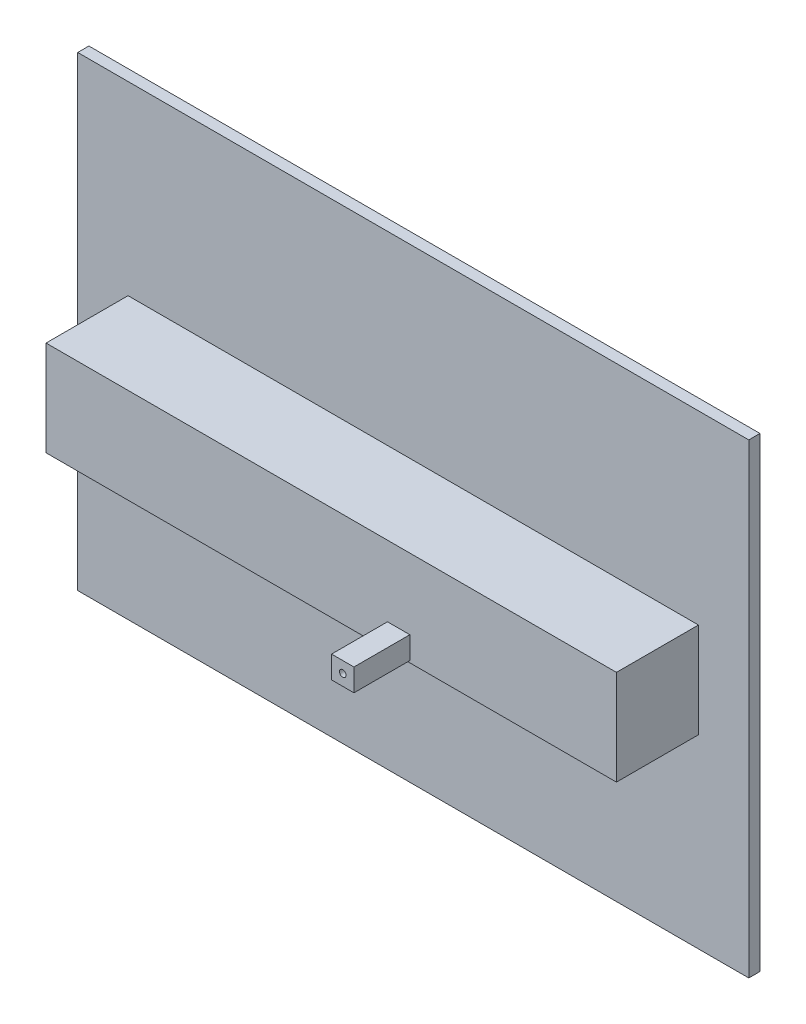
SolidWorks part; units mm, degrees
ref_plane "前视基准面" through (0, 0, 0) normal (0, 0, 1) x (1, 0, 0)
ref_plane "上视基准面" through (0, 0, 0) normal (0, 1, 0) x (1, 0, 0)
ref_plane "右视基准面" through (0, 0, 0) normal (1, 0, 0) x (0, 0, -1)
sketch "草图1" plane through (0, 0, 0) normal (0, 0, 1) x (1, 0, 0)
  line L1 (-90, 62.5) -> (90, 62.5)
  line L2 (-90, 62.5) -> (-90, -62.5)
  line L3 (-90, -62.5) -> (90, -62.5)
  line L4 (90, 62.5) -> (90, -62.5)
  line L5 (-90, 62.5) -> (90, -62.5) construction
  line L6 (-90, -62.5) -> (90, 62.5) construction
  point P0 (0, 0)
  dimension "D1" = 125
  dimension "D2" = 180
extrude "凸台-拉伸1" add sketch "草图1" along normal blind 3
sketch "草图7" plane through (0, 0, 0) normal (0, 0, -1) x (-1, 0, 0)
  line L1 (-74, 10.25) -> (74, 10.25)
  line L2 (-74, 10.25) -> (-74, -10.25)
  line L3 (-74, -10.25) -> (74, -10.25)
  line L4 (74, 10.25) -> (74, -10.25)
  line L5 (0, 0) -> (72.729, 0) construction
  line L8 (0, 0) -> (0, -50.9103) construction
  dimension "D1" = 20.5
  dimension "D2" = 148
extrude "电池位切除-拉伸3" cut sketch "草图7" against normal up to next
sketch "草图8" plane through (0, 0, 3) normal (0, 0, 1) x (1, 0, 0)
  line L12 (74, 10.25) -> (74, -10.25) construction
  line L13 (-76.5, 12.75) -> (76.5, 12.75)
  line L14 (-76.5, 12.75) -> (-76.5, -12.75)
  line L15 (-76.5, -12.75) -> (76.5, -12.75)
  line L16 (76.5, 12.75) -> (76.5, -12.75)
  line L17 (-74, -10.25) -> (-74, 10.25) construction
  line L18 (-74, 10.25) -> (74, 10.25) construction
  line L19 (74, -10.25) -> (-74, -10.25) construction
  line L20 (-74, 10.25) -> (74, 10.25)
  line L21 (74, -10.25) -> (-74, -10.25)
  line L22 (74, 10.25) -> (74, -10.25)
  line L23 (-74, -10.25) -> (-74, 10.25) construction
  line L24 (-74, -10.25) -> (-74, 10.25)
  dimension "D1" = 2.5
  dimension "D2" = 2.5
  dimension "D3" = 2.5
  dimension "D4" = 2.5
extrude "凸台-拉伸2" add sketch "草图8" along normal blind 22
sketch "草图9" plane through (0, 0, 25) normal (0, 0, 1) x (1, 0, 0)
  line L0 (76.5, 12.75) -> (-76.5, 12.75) construction
  line L5 (76.5, 12.75) -> (-76.5, 12.75)
  line L6 (-76.5, -12.75) -> (76.5, -12.75) construction
  line L7 (-76.5, -12.75) -> (76.5, -12.75)
  line L8 (76.5, -12.75) -> (76.5, 12.75) construction
  line L9 (76.5, -12.75) -> (76.5, 12.75)
  line L10 (-76.5, 12.75) -> (-76.5, -12.75) construction
  line L11 (-76.5, 12.75) -> (-76.5, -12.75)
extrude "凸台-拉伸3" add sketch "草图9" against normal blind 2.5
sketch "草图4" plane through (0, 0, 0) normal (0, 0, -1) x (-1, 0, 0)
  line L0 (74, -10.25) -> (74, 10.25) construction
  line L5 (74, 0) -> (84.6307, 0) construction
  line L10 (83.2374, -53.4277) -> (79.3374, -53.4277) construction
  line L11 (83.2374, -49.6277) -> (83.2374, -53.4277) construction
  line L12 (79.3374, -49.6277) -> (83.2374, -49.6277) construction
  line L29 (74, -4) -> (78, -4)
  line L30 (78, -4) -> (78, 4)
  line L31 (78, 4) -> (74, 4)
  line L32 (74, 4) -> (74, -4)
  dimension "D1" = 8
  dimension "D2" = 4
extrude "切除-拉伸2" cut sketch "草图4" along normal blind 1.6 from surface starting at face at (0, 0, 3)
sketch "草图10" plane through (0, 0, 25) normal (0, 0, 1) x (1, 0, 0)
  line L0 (18.0886, -9.21) -> (8.5541, -9.21) construction
  line L2 (15.0886, -6.21) -> (15.0886, -12.21)
  line L4 (21.0886, -6.21) -> (21.0886, -12.21)
  line L5 (18.0886, -9.21) -> (18.0886, -3.21) construction
  line L6 (0, 0) -> (60.8594, 0) construction
  line L7 (0, 0) -> (0, 60.5) construction
  line L8 (75, 60.5) -> (-75, 60.5) construction
  line L9 (15.0886, -6.21) -> (21.0886, -6.21)
  line L10 (15.0886, -12.21) -> (21.0886, -12.21)
  circle A0 centre (18.0886, -9.21) radius 0.875
  dimension "D2" = 1.75
  dimension "D1" = 6
extrude "凸台-拉伸4" add sketch "草图10" along normal up to surface (15 mm away)
